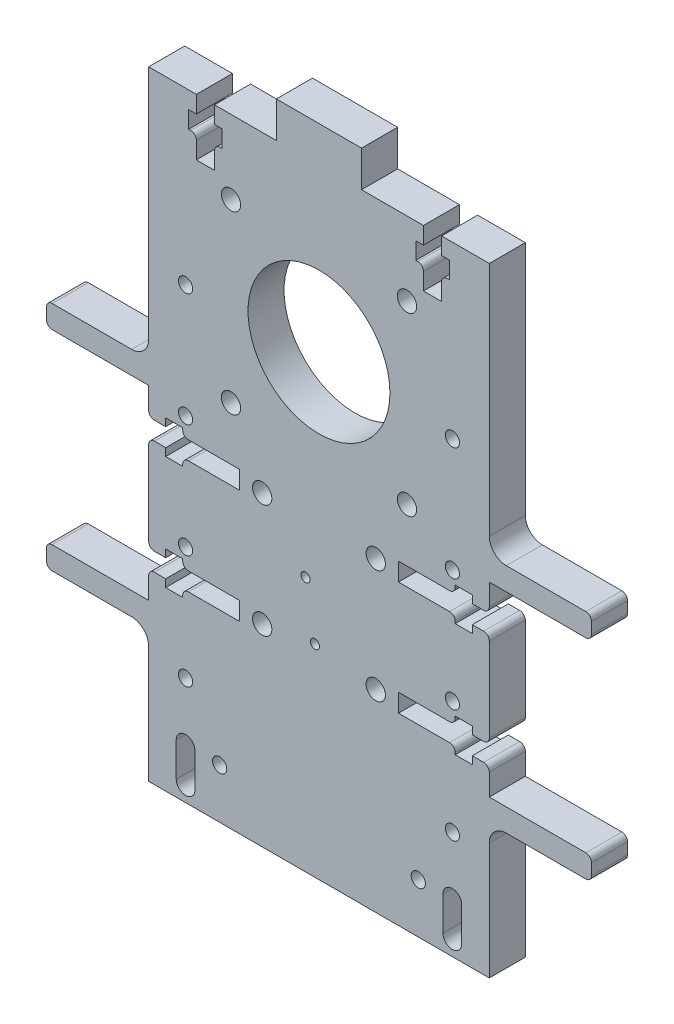
SolidWorks part; units mm, degrees
ref_plane "Front" through (0, 0, 0) normal (0, 0, 1) x (1, 0, 0)
ref_plane "Top" through (0, 0, 0) normal (0, 1, 0) x (1, 0, 0)
ref_plane "Right" through (0, 0, 0) normal (1, 0, 0) x (0, 0, -1)
ref_plane "Plane1" through (0, 0, 6.35) normal (0, 0, 1) x (1, 0, 0)
sketch "Sketch1" plane through (0, 0, 6.35) normal (0, 0, 1) x (1, 0, 0)
  line L0 (48, -56.9) -> (48, -52.9)
  line L1 (48, -52.9) -> (30, -52.9)
  line L2 (30, -52.9) -> (30, -48.1)
  line L3 (30, -48.1) -> (27, -48.1)
  line L4 (27, -48.1) -> (27, -49.45)
  line L5 (27, -49.45) -> (24, -49.45)
  line L6 (24, -49.45) -> (24, -48.1)
  line L7 (24, -48.1) -> (14, -48.1)
  line L8 (14, -48.1) -> (14, -44.9)
  line L9 (14, -44.9) -> (24, -44.9)
  line L10 (24, -44.9) -> (24, -43.55)
  line L11 (24, -43.55) -> (27, -43.55)
  line L12 (27, -43.55) -> (27, -44.9)
  line L13 (27, -44.9) -> (30, -44.9)
  line L14 (30, -44.9) -> (30, -28.1)
  line L15 (30, -28.1) -> (27, -28.1)
  line L16 (27, -28.1) -> (27, -29.45)
  line L17 (27, -29.45) -> (24, -29.45)
  line L18 (24, -29.45) -> (24, -28.1)
  line L19 (24, -28.1) -> (14, -28.1)
  line L20 (14, -28.1) -> (14, -24.9)
  line L21 (14, -24.9) -> (24, -24.9)
  line L22 (24, -24.9) -> (24, -23.55)
  line L23 (24, -23.55) -> (27, -23.55)
  line L24 (27, -23.55) -> (27, -24.9)
  line L25 (27, -24.9) -> (30, -24.9)
  line L26 (30, -24.9) -> (30, -20.1)
  line L27 (30, -20.1) -> (48, -20.1)
  line L28 (48, -20.1) -> (48, -16.1)
  line L29 (48, -16.1) -> (30, -16.1)
  line L30 (30, -16.1) -> (30, 28.5)
  line L31 (30, 28.5) -> (21.6, 28.5)
  line L32 (21.6, 28.5) -> (21.6, 25.5)
  line L33 (21.6, 25.5) -> (22.95, 25.5)
  line L34 (22.95, 25.5) -> (22.95, 22.5)
  line L35 (22.95, 22.5) -> (21.6, 22.5)
  line L36 (21.6, 22.5) -> (21.6, 18.5)
  line L37 (21.6, 18.5) -> (18.4, 18.5)
  line L38 (18.4, 18.5) -> (18.4, 22.5)
  line L39 (18.4, 22.5) -> (17.05, 22.5)
  line L40 (17.05, 22.5) -> (17.05, 25.5)
  line L41 (17.05, 25.5) -> (18.4, 25.5)
  line L42 (18.4, 25.5) -> (18.4, 28.5)
  line L43 (18.4, 28.5) -> (7.5, 28.5)
  line L44 (7.5, 28.5) -> (7.5, 34.85)
  line L45 (7.5, 34.85) -> (-7.5, 34.85)
  line L46 (-7.5, 34.85) -> (-7.5, 28.5)
  line L47 (-7.5, 28.5) -> (-18.4, 28.5)
  line L48 (-18.4, 28.5) -> (-18.4, 25.5)
  line L49 (-18.4, 25.5) -> (-17.05, 25.5)
  line L50 (-17.05, 25.5) -> (-17.05, 22.5)
  line L51 (-17.05, 22.5) -> (-18.4, 22.5)
  line L52 (-18.4, 22.5) -> (-18.4, 18.5)
  line L53 (-18.4, 18.5) -> (-21.6, 18.5)
  line L54 (-21.6, 18.5) -> (-21.6, 22.5)
  line L55 (-21.6, 22.5) -> (-22.95, 22.5)
  line L56 (-22.95, 22.5) -> (-22.95, 25.5)
  line L57 (-22.95, 25.5) -> (-21.6, 25.5)
  line L58 (-21.6, 25.5) -> (-21.6, 28.5)
  line L59 (-21.6, 28.5) -> (-30, 28.5)
  line L60 (-30, 28.5) -> (-30, -16.1)
  line L61 (-30, -16.1) -> (-48, -16.1)
  line L62 (-48, -16.1) -> (-48, -20.1)
  line L63 (-48, -20.1) -> (-30, -20.1)
  line L64 (-30, -20.1) -> (-30, -24.9)
  line L65 (-30, -24.9) -> (-27, -24.9)
  line L66 (-27, -24.9) -> (-27, -23.55)
  line L67 (-27, -23.55) -> (-24, -23.55)
  line L68 (-24, -23.55) -> (-24, -24.9)
  line L69 (-24, -24.9) -> (-14, -24.9)
  line L70 (-14, -24.9) -> (-14, -28.1)
  line L71 (-14, -28.1) -> (-24, -28.1)
  line L72 (-24, -28.1) -> (-24, -29.45)
  line L73 (-24, -29.45) -> (-27, -29.45)
  line L74 (-27, -29.45) -> (-27, -28.1)
  line L75 (-27, -28.1) -> (-30, -28.1)
  line L76 (-30, -28.1) -> (-30, -44.9)
  line L77 (-30, -44.9) -> (-27, -44.9)
  line L78 (-27, -44.9) -> (-27, -43.55)
  line L79 (-27, -43.55) -> (-24, -43.55)
  line L80 (-24, -43.55) -> (-24, -44.9)
  line L81 (-24, -44.9) -> (-14, -44.9)
  line L82 (-14, -44.9) -> (-14, -48.1)
  line L83 (-14, -48.1) -> (-24, -48.1)
  line L84 (-24, -48.1) -> (-24, -49.45)
  line L85 (-24, -49.45) -> (-27, -49.45)
  line L86 (-27, -49.45) -> (-27, -48.1)
  line L87 (-27, -48.1) -> (-30, -48.1)
  line L88 (-30, -48.1) -> (-30, -52.9)
  line L89 (-30, -52.9) -> (-48, -52.9)
  line L90 (-48, -52.9) -> (-48, -56.9)
  line L91 (-48, -56.9) -> (-30, -56.9)
  line L92 (-30, -56.9) -> (-30, -80.5)
  line L93 (-30, -80.5) -> (30, -80.5)
  line L94 (30, -80.5) -> (30, -56.9)
  line L95 (30, -56.9) -> (48, -56.9)
  line L96 (-21.8424, -71.75) -> (-21.8424, -77.75)
  line L97 (-25.1424, -77.75) -> (-25.1424, -71.75)
  line L98 (21.8424, -77.75) -> (21.8424, -71.75)
  line L99 (25.1424, -71.75) -> (25.1424, -77.75)
  arc A0 (-25.1424, -71.75) -> (-21.8424, -71.75) centre (-23.4924, -71.75) cw
  arc A1 (-21.8424, -77.75) -> (-25.1424, -77.75) centre (-23.4924, -77.75) cw
  arc A2 (25.1424, -77.75) -> (21.8424, -77.75) centre (23.4924, -77.75) cw
  arc A3 (21.8424, -71.75) -> (25.1424, -71.75) centre (23.4924, -71.75) cw
extrude "Boss-Extrude1" add sketch "Sketch1" against normal blind 6.35
fillet "Fillet1" radius 1 24 edges at (-48, -16.1, 3.175) (48, -16.1, 3.175) (48, -56.9, 3.175) (30, -24.9, 3.175) (-30, -44.9, 3.175) (30, -28.1, 3.175) (-30, -24.9, 3.175) (30, -44.9, 3.175) (-30, -48.1, 3.175) (30, -48.1, 3.175) (-30, -28.1, 3.175) (-24, -48.1, 3.175) (-24, -44.9, 3.175) (-24, -28.1, 3.175) (-24, -24.9, 3.175) (24, -28.1, 3.175) (24, -24.9, 3.175) (24, -48.1, 3.175) (24, -44.9, 3.175) (48, -52.9, 3.175) (48, -20.1, 3.175) (-48, -56.9, 3.175) (-48, -52.9, 3.175) (-48, -20.1, 3.175) tangent propagation no
fillet "Fillet3" radius 3 4 edges at (-30, -16.1, 3.175) (30, -16.1, 3.175) (-30, -56.9, 3.175) (30, -56.9, 3.175) tangent propagation no
hole_wizard "M2 Tapped Hole1" positions "Sketch3" profile "Sketch2" tap size "M2" standard "ISO" end condition through all
sketch "Sketch3" plane through (0, 0, 6.35) normal (0, 0, 1) x (1, 0, 0)
  point P0 (-2.3593, -35.5451)
sketch "Sketch2" plane through (-2.3593, -35.5451, 6.35) normal (1, 0, 0) x (0, -1, 0)
  line L0 (0, 0) -> (0, 6.35)
  line L1 (0, 6.35) -> (0.8, 6.35)
  line L2 (0.8, 6.35) -> (0.8, 0)
  line L5 (0.8, 0) -> (0, 0)
  line L11 (0, -6.35) -> (0, 107.95) construction
  dimension "Thru Tap Drill Dia." = 1.6
  dimension "Thru Tap Drill Depth" = 6.35
cosmetic thread "Hole Thread11" parameters "D2"=2
hole_wizard "M2 Tapped Hole2" positions "Sketch5" profile "Sketch4" tap size "M2" standard "ISO" end condition through all
sketch "Sketch5" plane through (0, 0, 6.35) normal (0, 0, 1) x (1, 0, 0)
  point P0 (-0.7096, -44.9008)
sketch "Sketch4" plane through (-0.7096, -44.9008, 6.35) normal (1, 0, 0) x (0, -1, 0)
  line L0 (0, 0) -> (0, 6.35)
  line L1 (0, 6.35) -> (0.8, 6.35)
  line L2 (0.8, 6.35) -> (0.8, 0)
  line L5 (0.8, 0) -> (0, 0)
  line L11 (0, -6.35) -> (0, 107.95) construction
  dimension "Thru Tap Drill Dia." = 1.6
  dimension "Thru Tap Drill Depth" = 6.35
cosmetic thread "Hole Thread12" parameters "D2"=2
hole_wizard "M3 Clearance Hole1" positions "Sketch7" profile "Sketch6" hole size "M3" standard "ISO" end condition through all
sketch "Sketch7" plane through (0, 0, 6.35) normal (0, 0, 1) x (1, 0, 0)
  point P0 (15.5, 15.5)
sketch "Sketch6" plane through (15.5, 15.5, 6.35) normal (1, 0, 0) x (0, -1, 0)
  line L0 (0, 0) -> (0, 6.35)
  line L1 (0, 6.35) -> (1.7, 6.35)
  line L2 (1.7, 6.35) -> (1.7, 0)
  line L5 (1.7, 0) -> (0, 0)
  line L11 (0, -6.35) -> (0, 107.95) construction
  dimension "Thru Hole Dia." = 3.4
  dimension "Thru Hole Depth" = 6.35
hole_wizard "M3 Clearance Hole2" positions "Sketch9" profile "Sketch8" hole size "M3" standard "ISO" end condition through all
sketch "Sketch9" plane through (0, 0, 6.35) normal (0, 0, 1) x (1, 0, 0)
  point P0 (-15.5, -15.5)
sketch "Sketch8" plane through (-15.5, -15.5, 6.35) normal (1, 0, 0) x (0, -1, 0)
  line L0 (0, 0) -> (0, 6.35)
  line L1 (0, 6.35) -> (1.7, 6.35)
  line L2 (1.7, 6.35) -> (1.7, 0)
  line L5 (1.7, 0) -> (0, 0)
  line L11 (0, -6.35) -> (0, 107.95) construction
  dimension "Thru Hole Dia." = 3.4
  dimension "Thru Hole Depth" = 6.35
hole_wizard "M3 Clearance Hole3" positions "Sketch11" profile "Sketch10" hole size "M3" standard "ISO" end condition through all
sketch "Sketch11" plane through (0, 0, 6.35) normal (0, 0, 1) x (1, 0, 0)
  point P0 (15.5, -15.5)
sketch "Sketch10" plane through (15.5, -15.5, 6.35) normal (1, 0, 0) x (0, -1, 0)
  line L0 (0, 0) -> (0, 6.35)
  line L1 (0, 6.35) -> (1.7, 6.35)
  line L2 (1.7, 6.35) -> (1.7, 0)
  line L5 (1.7, 0) -> (0, 0)
  line L11 (0, -6.35) -> (0, 107.95) construction
  dimension "Thru Hole Dia." = 3.4
  dimension "Thru Hole Depth" = 6.35
hole_wizard "M3 Clearance Hole4" positions "Sketch13" profile "Sketch12" hole size "M3" standard "ISO" end condition through all
sketch "Sketch13" plane through (0, 0, 6.35) normal (0, 0, 1) x (1, 0, 0)
  point P0 (-15.5, 15.5)
sketch "Sketch12" plane through (-15.5, 15.5, 6.35) normal (1, 0, 0) x (0, -1, 0)
  line L0 (0, 0) -> (0, 6.35)
  line L1 (0, 6.35) -> (1.7, 6.35)
  line L2 (1.7, 6.35) -> (1.7, 0)
  line L5 (1.7, 0) -> (0, 0)
  line L11 (0, -6.35) -> (0, 107.95) construction
  dimension "Thru Hole Dia." = 3.4
  dimension "Thru Hole Depth" = 6.35
hole_wizard "M3 Tapped Hole2" positions "Sketch15" profile "Sketch14" tap size "M3" standard "ISO" end condition through all
sketch "Sketch15" plane through (0, 0, 6.35) normal (0, 0, 1) x (1, 0, 0)
  point P0 (23.5, -61.5)
sketch "Sketch14" plane through (23.5, -61.5, 6.35) normal (1, 0, 0) x (0, -1, 0)
  line L0 (0, 0) -> (0, 6.35)
  line L1 (0, 6.35) -> (1.25, 6.35)
  line L2 (1.25, 6.35) -> (1.25, 0)
  line L5 (1.25, 0) -> (0, 0)
  line L11 (0, -6.35) -> (0, 107.95) construction
  dimension "Thru Tap Drill Dia." = 2.5
  dimension "Thru Tap Drill Depth" = 6.35
cosmetic thread "Hole Thread1" parameters "D2"=3
hole_wizard "M3 Tapped Hole3" positions "Sketch17" profile "Sketch16" tap size "M3" standard "ISO" end condition through all
sketch "Sketch17" plane through (0, 0, 6.35) normal (0, 0, 1) x (1, 0, 0)
  point P0 (23.5, -41.5)
sketch "Sketch16" plane through (23.5, -41.5, 6.35) normal (1, 0, 0) x (0, -1, 0)
  line L0 (0, 0) -> (0, 6.35)
  line L1 (0, 6.35) -> (1.25, 6.35)
  line L2 (1.25, 6.35) -> (1.25, 0)
  line L5 (1.25, 0) -> (0, 0)
  line L11 (0, -6.35) -> (0, 107.95) construction
  dimension "Thru Tap Drill Dia." = 2.5
  dimension "Thru Tap Drill Depth" = 6.35
cosmetic thread "Hole Thread3" parameters "D2"=3
hole_wizard "M3 Tapped Hole4" positions "Sketch19" profile "Sketch18" tap size "M3" standard "ISO" end condition through all
sketch "Sketch19" plane through (0, 0, 6.35) normal (0, 0, 1) x (1, 0, 0)
  point P0 (23.5, -21.5)
sketch "Sketch18" plane through (23.5, -21.5, 6.35) normal (1, 0, 0) x (0, -1, 0)
  line L0 (0, 0) -> (0, 6.35)
  line L1 (0, 6.35) -> (1.25, 6.35)
  line L2 (1.25, 6.35) -> (1.25, 0)
  line L5 (1.25, 0) -> (0, 0)
  line L11 (0, -6.35) -> (0, 107.95) construction
  dimension "Thru Tap Drill Dia." = 2.5
  dimension "Thru Tap Drill Depth" = 6.35
cosmetic thread "Hole Thread4" parameters "D2"=3
hole_wizard "M3 Tapped Hole5" positions "Sketch21" profile "Sketch20" tap size "M3" standard "ISO" end condition through all
sketch "Sketch21" plane through (0, 0, 6.35) normal (0, 0, 1) x (1, 0, 0)
  point P0 (23.5, -1.5)
sketch "Sketch20" plane through (23.5, -1.5, 6.35) normal (1, 0, 0) x (0, -1, 0)
  line L0 (0, 0) -> (0, 6.35)
  line L1 (0, 6.35) -> (1.25, 6.35)
  line L2 (1.25, 6.35) -> (1.25, 0)
  line L5 (1.25, 0) -> (0, 0)
  line L11 (0, -6.35) -> (0, 107.95) construction
  dimension "Thru Tap Drill Dia." = 2.5
  dimension "Thru Tap Drill Depth" = 6.35
cosmetic thread "Hole Thread5" parameters "D2"=3
hole_wizard "M3 Tapped Hole6" positions "Sketch23" profile "Sketch22" tap size "M3" standard "ISO" end condition through all
sketch "Sketch23" plane through (0, 0, 6.35) normal (0, 0, 1) x (1, 0, 0)
  point P0 (-17.4924, -71.75)
sketch "Sketch22" plane through (-17.4924, -71.75, 6.35) normal (1, 0, 0) x (0, -1, 0)
  line L0 (0, 0) -> (0, 6.35)
  line L1 (0, 6.35) -> (1.25, 6.35)
  line L2 (1.25, 6.35) -> (1.25, 0)
  line L5 (1.25, 0) -> (0, 0)
  line L11 (0, -6.35) -> (0, 107.95) construction
  dimension "Thru Tap Drill Dia." = 2.5
  dimension "Thru Tap Drill Depth" = 6.35
cosmetic thread "Hole Thread6" parameters "D2"=3
hole_wizard "M3 Tapped Hole7" positions "Sketch25" profile "Sketch24" tap size "M3" standard "ISO" end condition through all
sketch "Sketch25" plane through (0, 0, 6.35) normal (0, 0, 1) x (1, 0, 0)
  point P0 (17.4924, -71.75)
sketch "Sketch24" plane through (17.4924, -71.75, 6.35) normal (1, 0, 0) x (0, -1, 0)
  line L0 (0, 0) -> (0, 6.35)
  line L1 (0, 6.35) -> (1.25, 6.35)
  line L2 (1.25, 6.35) -> (1.25, 0)
  line L5 (1.25, 0) -> (0, 0)
  line L11 (0, -6.35) -> (0, 107.95) construction
  dimension "Thru Tap Drill Dia." = 2.5
  dimension "Thru Tap Drill Depth" = 6.35
cosmetic thread "Hole Thread7" parameters "D2"=3
hole_wizard "M3 Tapped Hole8" positions "Sketch27" profile "Sketch26" tap size "M3" standard "ISO" end condition through all
sketch "Sketch27" plane through (0, 0, 6.35) normal (0, 0, 1) x (1, 0, 0)
  point P0 (-23.5, -41.5)
sketch "Sketch26" plane through (-23.5, -41.5, 6.35) normal (1, 0, 0) x (0, -1, 0)
  line L0 (0, 0) -> (0, 6.35)
  line L1 (0, 6.35) -> (1.25, 6.35)
  line L2 (1.25, 6.35) -> (1.25, 0)
  line L5 (1.25, 0) -> (0, 0)
  line L11 (0, -6.35) -> (0, 107.95) construction
  dimension "Thru Tap Drill Dia." = 2.5
  dimension "Thru Tap Drill Depth" = 6.35
cosmetic thread "Hole Thread8" parameters "D2"=3
hole_wizard "M3 Tapped Hole9" positions "Sketch29" profile "Sketch28" tap size "M3" standard "ISO" end condition through all
sketch "Sketch29" plane through (0, 0, 6.35) normal (0, 0, 1) x (1, 0, 0)
  point P0 (-23.5, -61.5)
sketch "Sketch28" plane through (-23.5, -61.5, 6.35) normal (1, 0, 0) x (0, -1, 0)
  line L0 (0, 0) -> (0, 6.35)
  line L1 (0, 6.35) -> (1.25, 6.35)
  line L2 (1.25, 6.35) -> (1.25, 0)
  line L5 (1.25, 0) -> (0, 0)
  line L11 (0, -6.35) -> (0, 107.95) construction
  dimension "Thru Tap Drill Dia." = 2.5
  dimension "Thru Tap Drill Depth" = 6.35
cosmetic thread "Hole Thread9" parameters "D2"=3
hole_wizard "M3 Tapped Hole10" positions "Sketch31" profile "Sketch30" tap size "M3" standard "ISO" end condition through all
sketch "Sketch31" plane through (0, 0, 6.35) normal (0, 0, 1) x (1, 0, 0)
  point P0 (-23.5, -21.5)
sketch "Sketch30" plane through (-23.5, -21.5, 6.35) normal (1, 0, 0) x (0, -1, 0)
  line L0 (0, 0) -> (0, 6.35)
  line L1 (0, 6.35) -> (1.25, 6.35)
  line L2 (1.25, 6.35) -> (1.25, 0)
  line L5 (1.25, 0) -> (0, 0)
  line L11 (0, -6.35) -> (0, 107.95) construction
  dimension "Thru Tap Drill Dia." = 2.5
  dimension "Thru Tap Drill Depth" = 6.35
cosmetic thread "Hole Thread10" parameters "D2"=3
hole_wizard "M3 Clearance Hole8" positions "Sketch33" profile "Sketch32" hole size "M3" standard "ISO" end condition through all
sketch "Sketch33" plane through (0, 0, 6.35) normal (0, 0, 1) x (1, 0, 0)
  point P0 (-10, -46.5)
sketch "Sketch32" plane through (-10, -46.5, 6.35) normal (1, 0, 0) x (0, -1, 0)
  line L0 (0, 0) -> (0, 6.35)
  line L1 (0, 6.35) -> (1.7, 6.35)
  line L2 (1.7, 6.35) -> (1.7, 0)
  line L5 (1.7, 0) -> (0, 0)
  line L11 (0, -6.35) -> (0, 107.95) construction
  dimension "Thru Hole Dia." = 3.4
  dimension "Thru Hole Depth" = 6.35
hole_wizard "M3 Clearance Hole7" positions "Sketch35" profile "Sketch34" hole size "M3" standard "ISO" end condition through all
sketch "Sketch35" plane through (0, 0, 6.35) normal (0, 0, 1) x (1, 0, 0)
  point P0 (10, -46.5)
sketch "Sketch34" plane through (10, -46.5, 6.35) normal (1, 0, 0) x (0, -1, 0)
  line L0 (0, 0) -> (0, 6.35)
  line L1 (0, 6.35) -> (1.7, 6.35)
  line L2 (1.7, 6.35) -> (1.7, 0)
  line L5 (1.7, 0) -> (0, 0)
  line L11 (0, -6.35) -> (0, 107.95) construction
  dimension "Thru Hole Dia." = 3.4
  dimension "Thru Hole Depth" = 6.35
hole_wizard "M3 Tapped Hole1" positions "Sketch37" profile "Sketch36" tap size "M3" standard "ISO" end condition through all
sketch "Sketch37" plane through (0, 0, 6.35) normal (0, 0, 1) x (1, 0, 0)
  point P0 (-23.5, -1.5)
sketch "Sketch36" plane through (-23.5, -1.5, 6.35) normal (1, 0, 0) x (0, -1, 0)
  line L0 (0, 0) -> (0, 6.35)
  line L1 (0, 6.35) -> (1.25, 6.35)
  line L2 (1.25, 6.35) -> (1.25, 0)
  line L5 (1.25, 0) -> (0, 0)
  line L11 (0, -6.35) -> (0, 107.95) construction
  dimension "Thru Tap Drill Dia." = 2.5
  dimension "Thru Tap Drill Depth" = 6.35
cosmetic thread "Hole Thread2" parameters "D2"=3
hole_wizard "M3 Clearance Hole6" positions "Sketch39" profile "Sketch38" hole size "M3" standard "ISO" end condition through all
sketch "Sketch39" plane through (0, 0, 6.35) normal (0, 0, 1) x (1, 0, 0)
  point P0 (10, -26.5)
sketch "Sketch38" plane through (10, -26.5, 6.35) normal (1, 0, 0) x (0, -1, 0)
  line L0 (0, 0) -> (0, 6.35)
  line L1 (0, 6.35) -> (1.7, 6.35)
  line L2 (1.7, 6.35) -> (1.7, 0)
  line L5 (1.7, 0) -> (0, 0)
  line L11 (0, -6.35) -> (0, 107.95) construction
  dimension "Thru Hole Dia." = 3.4
  dimension "Thru Hole Depth" = 6.35
hole_wizard "Ø25.0 (25) Diameter Hole1" positions "Sketch41" profile "Sketch40" hole size "Ø25.0" standard "ANSI Metric"
sketch "Sketch41" plane through (0, 0, 6.35) normal (0, 0, 1) x (1, 0, 0)
  point P0 (0, 0)
sketch "Sketch40" plane through (0, 0, 6.35) normal (1, 0, 0) x (0, -1, 0)
  line L0 (0, 0) -> (0, 6.35)
  line L1 (0, 6.35) -> (12.5, 6.35)
  line L2 (12.5, 6.35) -> (12.5, 0)
  line L5 (12.5, 0) -> (0, 0)
  line L11 (0, -6.35) -> (0, 107.95) construction
  dimension "Thru Hole Dia." = 25
  dimension "Thru Hole Depth" = 6.35
hole_wizard "M3 Clearance Hole5" positions "Sketch43" profile "Sketch42" hole size "M3" standard "ISO" end condition through all
sketch "Sketch43" plane through (0, 0, 6.35) normal (0, 0, 1) x (1, 0, 0)
  point P0 (-10, -26.5)
sketch "Sketch42" plane through (-10, -26.5, 6.35) normal (1, 0, 0) x (0, -1, 0)
  line L0 (0, 0) -> (0, 6.35)
  line L1 (0, 6.35) -> (1.7, 6.35)
  line L2 (1.7, 6.35) -> (1.7, 0)
  line L5 (1.7, 0) -> (0, 0)
  line L11 (0, -6.35) -> (0, 107.95) construction
  dimension "Thru Hole Dia." = 3.4
  dimension "Thru Hole Depth" = 6.35
fillet "Fillet4" radius 1 4 edges at (21.6, 22.5, 3.175) (18.4, 22.5, 3.175) (-18.4, 22.5, 3.175) (-21.6, 22.5, 3.175)
